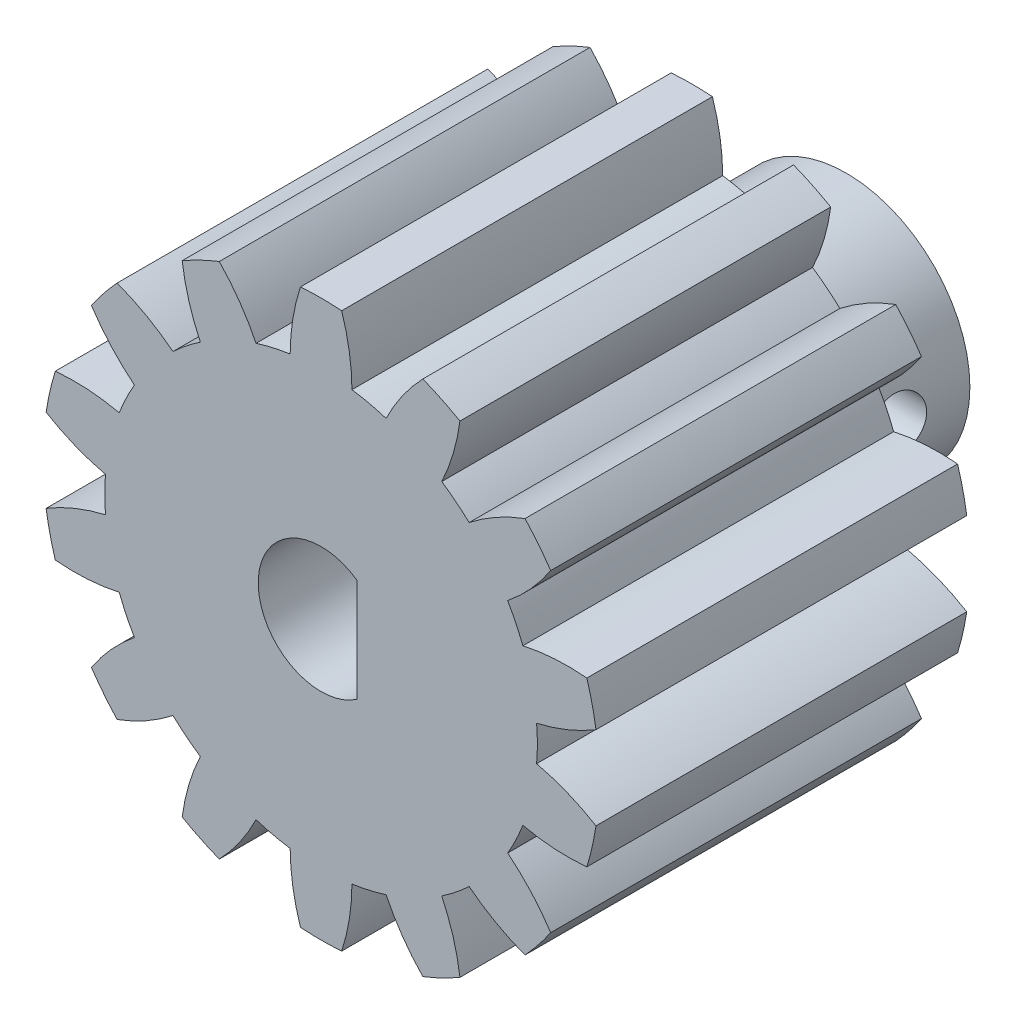
SolidWorks part; units mm, degrees
note: The reader was unsure of these and kept them because the rebuilt part matched: shared geometry of "Sketch2<4>".
ref_plane "Front Plane" through (0, 0, 0) normal (0, 0, 1) x (1, 0, 0)
ref_plane "Top Plane" through (0, 0, 0) normal (0, 1, 0) x (1, 0, 0)
ref_plane "Right Plane" through (0, 0, 0) normal (1, 0, 0) x (0, 0, -1)
sketch "Sketch1" plane through (0, 0, 0) normal (0, 0, 1) x (1, 0, 0)
  circle A12 centre (-24.1927, -27.8293) radius 6
  circle A15 centre (-24.1927, -27.8293) radius 3.05
  dimension "D3" = 12
  dimension "D1" = 6.1
extrude "Boss-Extrude1" add sketch "Sketch1" along normal up to vertex (7.5 mm away)
sketch "Sketch2" plane through (0, 0, 7.5) normal (0, 0, 1) x (1, 0, 0)
  line L0 (-24.1927, -14.3293) -> (-24.1927, -41.3293) construction
  circle A33 centre (-24.1927, -27.8293) radius 13.5
  circle A48 centre (-24.1927, -27.8293) radius 10.5
  circle A62 centre (-24.1927, -27.8293) radius 6 construction
  arc A63 (-25.1927, -14.3664) -> (-25.6927, -17.437) centre (-15.6928, -17.4893) ccw
  arc A64 (-23.1927, -14.3664) -> (-22.6927, -17.437) centre (-32.6925, -17.4893) cw
  point P1 (-18.1927, -27.8293)
  point P3 (-24.1927, -27.8293)
  point P13 (-16.5422, -25.4903)
  dimension "D1" = 27
  dimension "D3" = 2
  dimension "D4" = 10
  dimension "D5" = 3
  dimension "D2" = 3
extrude "Boss-Extrude3" add sketch "Sketch2" along normal blind 18
extrude "Boss-Extrude4" add sketch "Sketch2<4>" along normal up to surface (18 mm away) contours A33 L0 A48 A64 | L0 A33 A63 A48
sketch "Sketch2<4>" plane through (0, 0, 7.5) normal (0, 0, 1) x (1, 0, 0) same geometry as "Sketch2"
pattern_circular "CirPattern1" count 14 over 360 about axis through (-24.1927, -27.8293, 0) along (0, 0, 1) of "Boss-Extrude4"
sketch "Sketch3" plane through (0, 0, 7.5) normal (0, 0, -1) x (-1, 0, 0)
  circle A0 centre (24.1927, -27.8293) radius 3.05 construction
  circle A1 centre (24.1927, -27.8293) radius 3.05
extrude "Cut-Extrude1" cut sketch "Sketch3" against normal through all
sketch "Sketch5" plane through (0, 0, 0) normal (0, 0, -1) x (-1, 0, 0)
  line L1 (21.1427, -22.6623) -> (22.4427, -22.6623)
  line L2 (21.1427, -22.6623) -> (21.1427, -31.6503)
  line L3 (21.1427, -31.6503) -> (22.4427, -31.6503)
  line L4 (22.4427, -22.6623) -> (22.4427, -31.6503)
  circle A0 centre (24.1927, -27.8293) radius 6 construction
  circle A1 centre (24.1927, -27.8293) radius 3.05 construction
  dimension "D1" = 1.3
extrude "Boss-Extrude5" add sketch "Sketch5" against normal through all
sketch "Sketch4" plane through (0, 0, 0) normal (1, 0, 0) x (0, 0, -1)
  circle A1 centre (-3.5, -27.8293) radius 1.4
  circle A2 centre (-3.5, -27.8293) radius 1.4
  dimension "D1" = 0
extrude "Cut-Extrude2" cut sketch "Sketch4" against normal through all both and the other way through all
